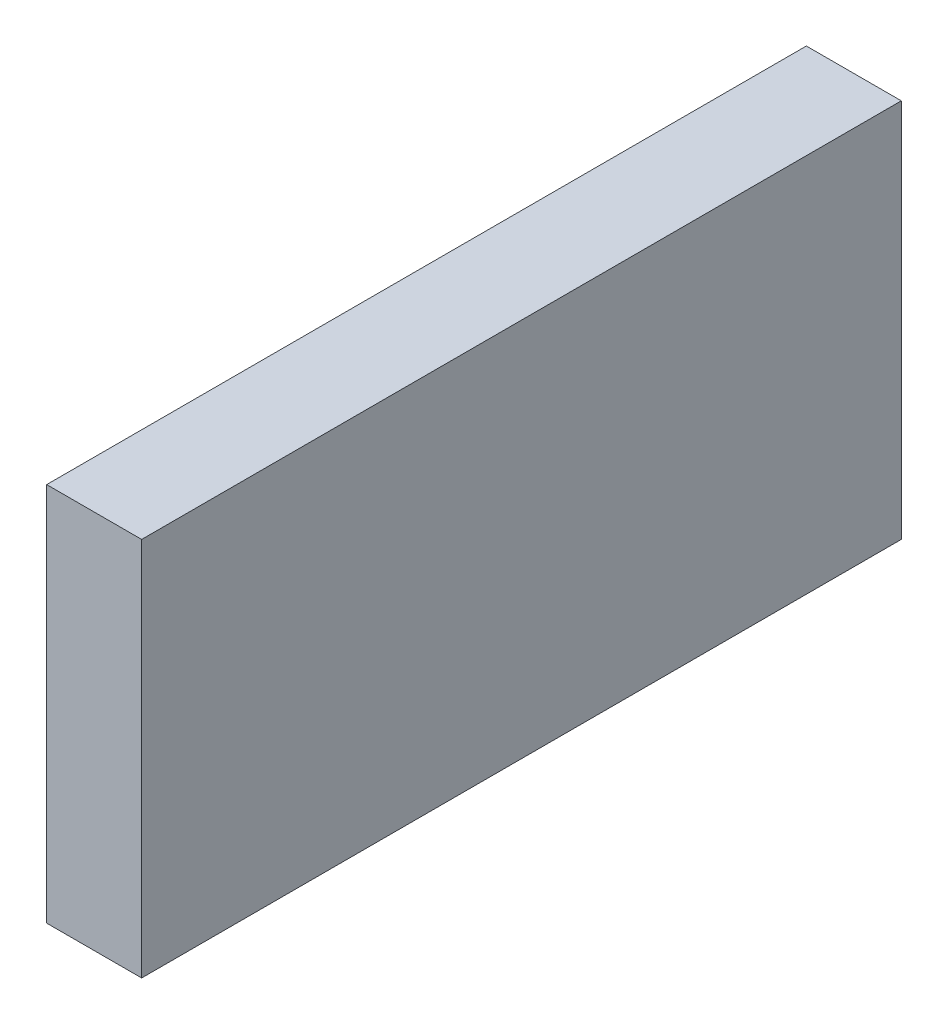
SolidWorks part; units mm, degrees
ref_plane "Front" through (0, 0, 0) normal (0, 0, 1) x (1, 0, 0)
ref_plane "Top" through (0, 0, 0) normal (0, 1, 0) x (1, 0, 0)
ref_plane "Right" through (0, 0, 0) normal (1, 0, 0) x (0, 0, -1)
sketch "Sketch1" plane through (0, 0, 0) normal (0, 0, 1) x (1, 0, 0)
  line L1 (-6.35, 25.4) -> (6.35, 25.4)
  line L2 (-6.35, 25.4) -> (-6.35, -25.4)
  line L3 (-6.35, -25.4) -> (6.35, -25.4)
  line L4 (6.35, 25.4) -> (6.35, -25.4)
  point P4 (0, 25.4)
  point P5 (6.35, 0)
  dimension "D1" = 12.7
  dimension "D2" = 50.8
extrude "Extrude1" add sketch "Sketch1" along normal mid plane 101.6
